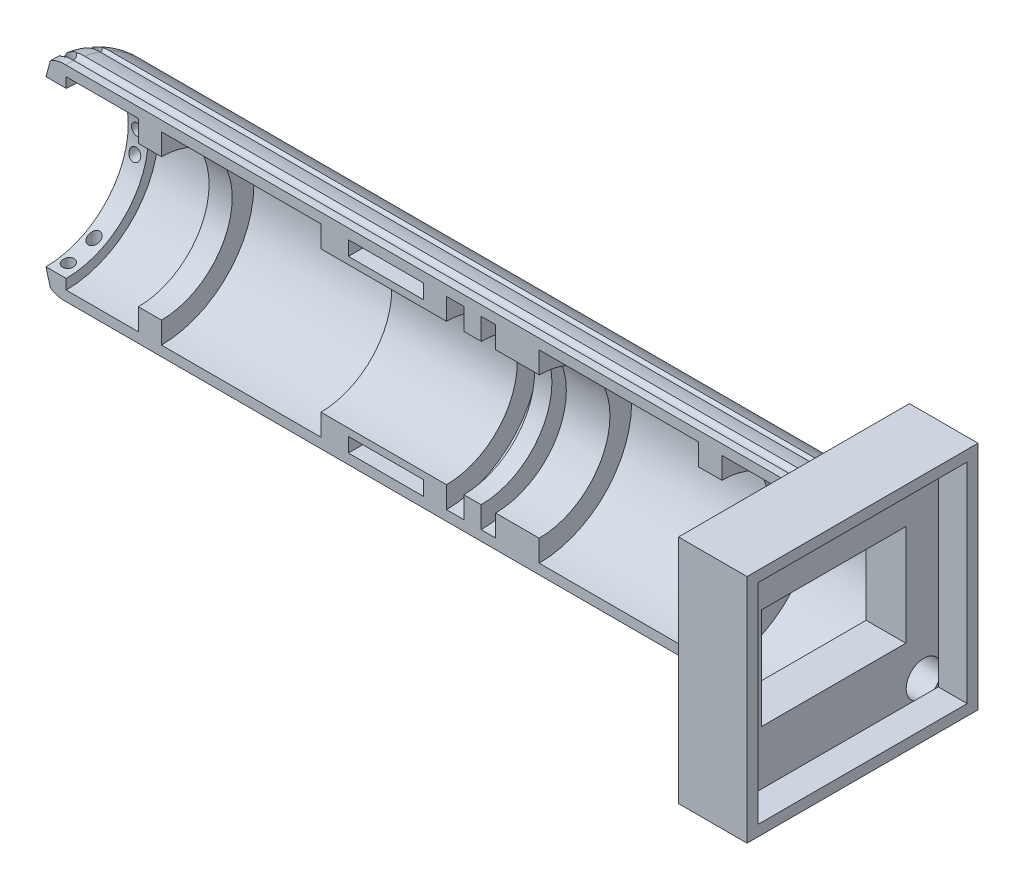
SolidWorks part; units mm, degrees
ref_plane "Front Plane" through (0, 0, 0) normal (0, 0, 1) x (1, 0, 0)
ref_plane "Top Plane" through (0, 0, 0) normal (0, 1, 0) x (1, 0, 0)
ref_plane "Right Plane" through (0, 0, 0) normal (1, 0, 0) x (0, 0, -1)
sketch "Sketch1" plane through (0, 0, 0) normal (0, 0, 1) x (1, 0, 0)
  line L1 (-17.1588, 0) -> (33.29, 0)
  line L5 (33.29, 0.7) -> (28.29, 0.7)
  line L6 (28.29, 0.7) -> (28.29, 2.2)
  line L7 (28.29, 2.2) -> (26.69, 2.2)
  line L8 (26.69, 2.2) -> (26.69, 0.7)
  line L9 (26.69, 0.7) -> (15.64, 0.7)
  line L10 (15.64, 0.7) -> (15.64, 2.2)
  line L11 (15.64, 2.2) -> (12.62, 2.2)
  line L12 (12.62, 2.2) -> (12.62, 0.7)
  line L13 (12.62, 0.7) -> (11.62, 0.7)
  line L14 (11.62, 0.7) -> (11.62, 2.2)
  line L15 (11.62, 2.2) -> (10.42, 2.2)
  line L16 (10.42, 2.2) -> (10.42, 0.7)
  line L17 (10.42, 0.7) -> (9.22, 0.7)
  line L18 (9.22, 0.7) -> (9.22, 2.2)
  line L19 (9.22, 2.2) -> (0.52, 2.2)
  line L20 (0.52, 2.2) -> (0.52, 0.7)
  line L21 (0.52, 0.7) -> (-10.53, 0.7)
  line L22 (-10.53, 0.7) -> (-10.53, 2.2)
  line L23 (-10.53, 2.2) -> (-12.13, 2.2)
  line L24 (-12.13, 2.2) -> (-12.13, 0.7)
  line L25 (-12.13, 0.7) -> (-17.13, 0.7)
  line L30 (-19.05, 7.1) -> (26.85, 7.1) construction
  line L31 (-17.13, 0.7) -> (-17.13, 1.4)
  line L44 (-18.53, 2.6794) -> (-18.53, -5.4306) construction
  line L45 (-18.53, 1.4) -> (-18.23, 0.2804)
  line L46 (-17.13, 1.4) -> (-18.53, 1.4)
  line L47 (33.29, 0.7) -> (33.29, 0)
  arc A1 (-17.1588, 0) -> (-18.23, 0.2804) centre (-17.2607, 1.7971) cw
  dimension "D24" = 1.8
  dimension "D2" = 0.7
  dimension "D3" = 0.7
  dimension "D4" = 0.7
  dimension "D5" = 0.7
  dimension "D6" = 0.7
  dimension "D8" = 5
  dimension "D9" = 1.6
  dimension "D10" = 11.05
  dimension "D11" = 6.4
  dimension "D12" = 3.02
  dimension "D13" = 1
  dimension "D14" = 1.2
  dimension "D15" = 1.2
  dimension "D16" = 8.7
  dimension "D17" = 11.05
  dimension "D18" = 1.6
  dimension "D19" = 5
  dimension "D20" = 0.7
  dimension "D21" = 1.5
  dimension "D22" = 1.4
  dimension "D23" = 105
  dimension "D25" = 0.3
revolve "Revolve1" add sketch "Sketch1" angle 180 about L30
sketch "Sketch3" plane through (0, 0, 0) normal (0, 0, 1) x (1, 0, 0)
  line L1 (2.42, 13.5) -> (7.62, 13.5)
  line L2 (2.42, 13.5) -> (2.42, 12.5)
  line L3 (2.42, 12.5) -> (7.62, 12.5)
  line L4 (7.62, 13.5) -> (7.62, 12.5)
  line L5 (2.42, 1.7) -> (7.62, 1.7)
  line L6 (2.42, 1.7) -> (2.42, 0.7)
  line L7 (2.42, 0.7) -> (7.62, 0.7)
  line L8 (7.62, 1.7) -> (7.62, 0.7)
  line L9 (0.52, 13.5) -> (0.52, 0.7) construction
  line L11 (-17.1588, 0) -> (33.29, 0) construction
  line L12 (-17.1588, 14.2) -> (33.29, 14.2) construction
  line L13 (0.52, 2.2) -> (0.52, 0.7) construction
  dimension "D1" = 5.2
  dimension "D2" = 1
  dimension "D3" = 1.9
  dimension "D4" = 5.2
  dimension "D5" = 1
  dimension "D6" = 1.9
  dimension "D7" = 0.7
  dimension "D8" = 0.7
extrude "Cut-Extrude1" cut sketch "Sketch3" against normal blind 1.5
sketch "Sketch4" plane through (0, 0, 0) normal (1, 0, 0) x (0, 0, -1)
  line L0 (0, 12) -> (0, 2.2) construction
  line L1 (0, 7.1) -> (0.9463, -0.088) construction
  line L2 (0, 7.1) -> (0.9463, 14.288) construction
  line L3 (0, 7.1) -> (2.7745, 13.7981) construction
  line L4 (0, 7.1) -> (7.0346, 8.8539) construction
  line L5 (3.12, 9.54) -> (3.12, 5.26) construction
  line L6 (0, 7.1) -> (7.0346, 5.3461) construction
  line L7 (0, 7.1) -> (2.7745, 0.4019) construction
  line L8 (3.12, 5.26) -> (-2.58, 5.26) construction
  line L9 (-2.58, 5.26) -> (-2.58, 9.54) construction
  line L10 (3.12, 9.54) -> (-2.58, 9.54) construction
  line L11 (7.25, 7.1) -> (-8.1279, 7.1) construction
  circle A0 centre (0.9463, 14.288) radius 0.4
  circle A1 centre (7.25, 7.1) radius 0.4
  circle A2 centre (2.7745, 13.7981) radius 0.4
  circle A3 centre (7.0346, 8.8539) radius 0.4
  circle A5 centre (7.0346, 5.3461) radius 0.4
  circle A6 centre (2.7745, 0.4019) radius 0.4
  circle A9 centre (0.9463, -0.088) radius 0.4
  dimension "D7" = 0.8
  dimension "D8" = 0.8
  dimension "D9" = 0.8
  dimension "D10" = 0.8
  dimension "D11" = 0.8
  dimension "D12" = 0.8
  dimension "D20" = 0.8
  dimension "D1" = 7.5
  dimension "D2" = 15
  dimension "D3" = 14
  dimension "D4" = 28
  dimension "D5" = 7.5
  dimension "D6" = 15
  dimension "D13" = 7.25
  dimension "D14" = 7.25
  dimension "D15" = 7.25
  dimension "D16" = 7.25
  dimension "D17" = 4.9
  dimension "D18" = 7.25
  dimension "D19" = 7.25
  dimension "D21" = 7.25
extrude "Cut-Extrude2" cut sketch "Sketch4" against normal blind 18
extrude "Cut-Extrude3" cut sketch "Sketch4<2>" along normal blind 40
sketch "Sketch4<2>" plane through (0, 0, 0) normal (1, 0, 0) x (0, 0, -1) same geometry as "Sketch4"
ref_plane "Plane1" through (-17.9, 0, 0) normal (-1, 0, 0) x (0, 0, 1)
sketch "Sketch5" plane through (-17.9, 0, 0) normal (-1, 0, 0) x (0, 0, 1)
  line L0 (0, 15.2573) -> (0, -1.603) construction
  line L1 (-0.9064, 13.9847) -> (-0.9064, 8.7383) construction
  line L34 (-0.5183, 10.0941) -> (-0.9183, 10.0941)
  line L35 (-0.5183, 10.0941) -> (-0.5183, 15.2573)
  line L36 (-0.5183, 15.2573) -> (-0.9183, 15.2573)
  line L37 (-0.9183, 10.0941) -> (-0.9183, 15.2573)
  arc A0 (-0.6558, 14.013) -> (-1.1558, 13.9472) centre (0, 7.1) ccw construction
  dimension "D1" = 0.4
revolve "Cut-Revolve1" cut sketch "Sketch5" angle 360 about L37
sketch "Sketch6" plane through (-17.9, 0, 0) normal (-1, 0, 0) x (0, 0, 1)
  line L0 (-2.6574, 13.5155) -> (-2.6574, 8.0754) construction
  line L7 (-2.2924, 10.6444) -> (-2.6924, 10.6444)
  line L8 (-2.2924, 10.6444) -> (-2.2924, 14.9594)
  line L9 (-2.2924, 14.9594) -> (-2.6924, 14.9594)
  line L10 (-2.6924, 10.6444) -> (-2.6924, 14.9594)
  arc A1 (-2.4227, 13.6078) -> (-2.8886, 13.4148) centre (0, 7.1) ccw construction
  dimension "D1" = 0.4
revolve "Cut-Revolve2" cut sketch "Sketch6" angle 360 about L10
sketch "Sketch7" plane through (-17.9, 0, 0) normal (-1, 0, 0) x (0, 0, 1)
  line L0 (0.0425, 8.7799) -> (-7.1978, 8.7799) construction
  line L1 (-7.1978, 8.7799) -> (-7.1851, 9.1799)
  line L2 (-7.1851, 9.1799) -> (-4.5851, 9.1799)
  line L3 (-4.5851, 9.1799) -> (-4.5978, 8.7799)
  line L4 (-4.5978, 8.7799) -> (-7.1978, 8.7799)
  line L5 (-6.7378, 8.7799) -> (0.3284, 8.7799) construction
  arc A0 (-6.6724, 9.0235) -> (-6.7944, 8.5341) centre (0, 7.1) ccw construction
  dimension "D1" = 0.4
  dimension "D2" = 2.6
  dimension "D3" = 2.6
  dimension "D4" = 0.4
  dimension "D5" = 0
revolve "Cut-Revolve3" cut sketch "Sketch7" angle 360 about L0
sketch "Sketch8" plane through (-17.9, 0, 0) normal (-1, 0, 0) x (0, 0, 1)
  line L0 (-7.1321, 5.6953) -> (-0.7821, 5.6953) construction
  line L6 (-7.1321, 5.6953) -> (-4.2266, 5.6953)
  line L7 (-7.1321, 5.6953) -> (-7.1321, 5.2953)
  line L8 (-7.1321, 5.2953) -> (-4.2266, 5.2953)
  line L9 (-4.2266, 5.6953) -> (-4.2266, 5.2953)
  dimension "D1" = 0.4
revolve "Cut-Revolve4" cut sketch "Sketch8" angle 360 about L0
sketch "Sketch17" plane through (-17.9, 0, 0) normal (-1, 0, 0) x (0, 0, 1)
  line L0 (-7.567, 7.1) -> (-0.9981, 7.1) construction
  line L2 (-7.1845, 7.1) -> (-4.5845, 7.1)
  line L3 (-7.1845, 7.1) -> (-7.1845, 6.7)
  line L4 (-7.1845, 6.7) -> (-4.5845, 6.7)
  line L5 (-4.5845, 7.1) -> (-4.5845, 6.7)
  dimension "D1" = 0.4
  dimension "D2" = 2.6
revolve "Cut-Revolve7" cut sketch "Sketch17" angle 360 about L0
sketch "Sketch9" plane through (-17.9, 0, 0) normal (-1, 0, 0) x (0, 0, 1)
  line L0 (-2.6574, 0.6845) -> (-2.6574, 8.9964) construction
  line L6 (-2.6924, 0.2752) -> (-2.2924, 0.2752)
  line L7 (-2.6924, 0.2752) -> (-2.6924, 3.5751)
  line L8 (-2.6924, 3.5751) -> (-2.2924, 3.5751)
  line L9 (-2.2924, 0.2752) -> (-2.2924, 3.5751)
  arc A0 (-2.8886, 0.7852) -> (-2.4227, 0.5922) centre (0, 7.1) ccw construction
  dimension "D1" = 0.4
  dimension "D2" = 3.3
revolve "Cut-Revolve5" cut sketch "Sketch9" angle 360 about L7
sketch "Sketch10" plane through (-17.9, 0, 0) normal (-1, 0, 0) x (0, 0, 1)
  line L0 (-0.9183, 0.2225) -> (-0.9183, 7.6514) construction
  line L6 (-0.9183, 0.3476) -> (-0.5183, 0.3476)
  line L7 (-0.9183, 0.3476) -> (-0.9183, 3.2879)
  line L8 (-0.9183, 3.2879) -> (-0.5183, 3.2879)
  line L9 (-0.5183, 0.3476) -> (-0.5183, 3.2879)
  dimension "D1" = 0.4
revolve "Cut-Revolve6" cut sketch "Sketch10" angle 360 about L0
ref_plane "Plane2" through (33.29, 0, 0) normal (1, 0, 0) x (0, 0, -1)
sketch "Sketch11" plane through (33.29, 0, 0) normal (1, 0, 0) x (0, 0, -1)
  line L0 (0, 12) -> (0, 2.2) construction
  line L1 (-5, 10.6) -> (5, 10.6)
  line L2 (-5, 10.6) -> (-5, 3.6)
  line L3 (-5, 3.6) -> (5, 3.6)
  line L4 (5, 10.6) -> (5, 3.6)
  line L5 (0, 7.1) -> (-9.7594, 7.1) construction
  line L7 (-8, 15.1) -> (8, 15.1)
  line L8 (-8, 15.1) -> (-8, -0.9)
  line L9 (-8, -0.9) -> (8, -0.9)
  line L10 (8, 15.1) -> (8, -0.9)
  dimension "D1" = 3.5
  dimension "D2" = 7
  dimension "D3" = 5
  dimension "D4" = 10
  dimension "D5" = 16
  dimension "D6" = 8
  dimension "D7" = 16
  dimension "D8" = 8
extrude "Boss-Extrude1" add sketch "Sketch11" along normal blind 4.75
ref_plane "Plane3" through (38.04, 0, 0) normal (1, 0, 0) x (0, 0, -1)
sketch "Sketch12" plane through (38.04, 0, 0) normal (1, 0, 0) x (0, 0, -1)
  line L0 (0, 15.1) -> (0, -0.9) construction
  line L1 (-7.25, 14.35) -> (7.25, 14.35)
  line L2 (-7.25, 14.35) -> (-7.25, -0.15)
  line L3 (-7.25, -0.15) -> (7.25, -0.15)
  line L4 (7.25, 14.35) -> (7.25, -0.15)
  line L5 (8, 15.1) -> (-8, 15.1) construction
  line L6 (-8, -0.9) -> (8, -0.9) construction
  line L7 (0, 7.1) -> (-12.2604, 7.1) construction
  dimension "D1" = 14.5
  dimension "D2" = 14.5
  dimension "D3" = 7.25
  dimension "D4" = 7.25
extrude "Cut-Extrude4" cut sketch "Sketch12" against normal blind 2
ref_plane "Plane4" through (36.04, 0, 0) normal (1, 0, 0) x (0, 0, -1)
sketch "Sketch18" plane through (36.04, 0, 0) normal (1, 0, 0) x (0, 0, -1)
  line L0 (0, -2.427) -> (0, 16.9229) construction
  line L1 (-14.6814, 7.1) -> (18.9175, 7.1) construction
  line L2 (7.25, 14.35) -> (-7.25, 14.35) construction
  circle A0 centre (-6.25, 13.35) radius 1.225
  circle A1 centre (6.25, 0.85) radius 1.225
  circle A2 centre (6.25, 13.35) radius 0.65
  circle A3 centre (-6.25, 0.85) radius 0.65
  dimension "D1" = 2.45
  dimension "D2" = 2.45
  dimension "D8" = 1.3
  dimension "D9" = 1.3
  dimension "D3" = 12.5
  dimension "D4" = 6.25
  dimension "D5" = 12.5
  dimension "D6" = 7.25
  dimension "D7" = 6.25
  dimension "D10" = 12.5
  dimension "D11" = 12.5
  dimension "D12" = 12.5
extrude "Cut-Extrude5" cut sketch "Sketch18" against normal blind 5
ref_plane "Plane5" through (33.29, 0, 0) normal (-1, 0, 0) x (0, 0, 1)
sketch "Sketch19" plane through (33.29, 0, 0) normal (-1, 0, 0) x (0, 0, 1)
  circle A0 centre (-6.25, 13.35) radius 1.2
  circle A1 centre (6.25, 0.85) radius 1.2
  dimension "D1" = 2.4
  dimension "D2" = 2.4
extrude "Cut-Extrude6" cut sketch "Sketch19" against normal blind 1.3
